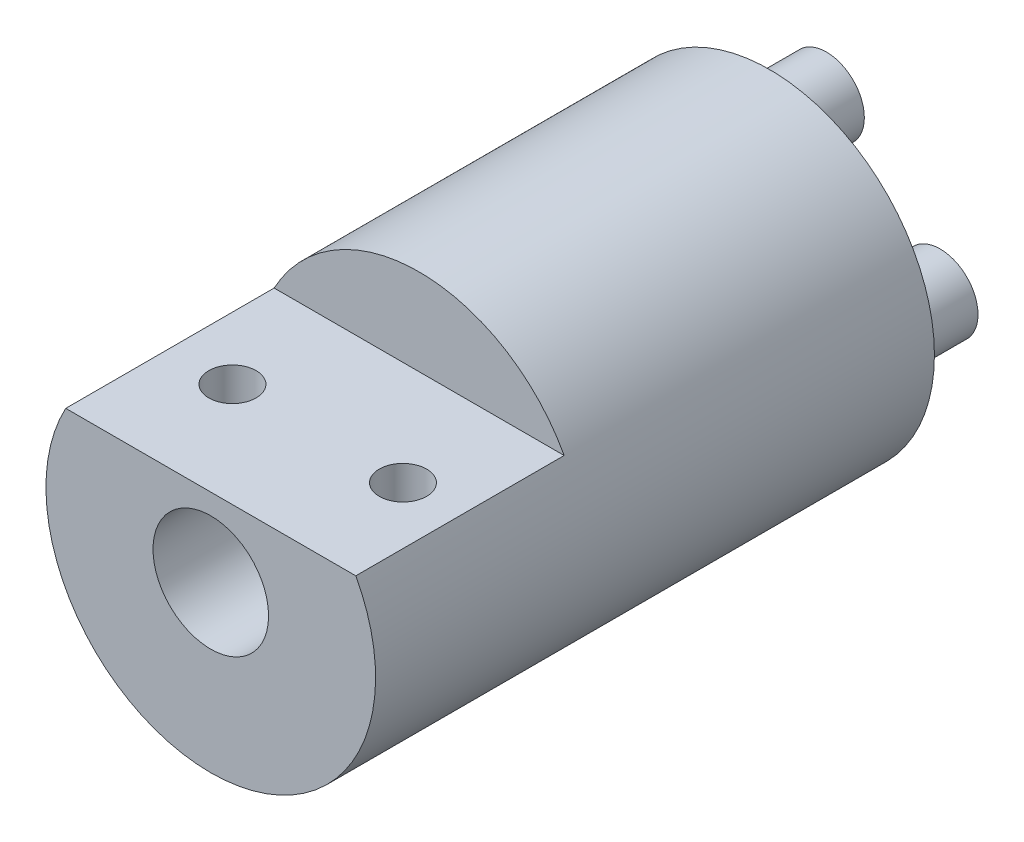
SolidWorks part; units mm, degrees
ref_plane "Front Plane" through (0, 0, 0) normal (0, 0, 1) x (1, 0, 0)
ref_plane "Top Plane" through (0, 0, 0) normal (0, 1, 0) x (1, 0, 0)
ref_plane "Right Plane" through (0, 0, 0) normal (1, 0, 0) x (0, 0, -1)
sketch "Sketch1" plane through (0, 0, 0) normal (0, 0, 1) x (1, 0, 0)
  circle A0 centre (0, 0) radius 8.7
  dimension "D1" = 17.4
extrude "Boss-Extrude1" add sketch "Sketch1" along normal blind 29.5 contours A0
sketch "Sketch2" plane through (0, 0, 29.5) normal (0, 0, 1) x (1, 0, 0)
  line L1 (-7.6555, 8.7) -> (9.3445, 8.7)
  line L2 (-7.6555, 8.7) -> (-7.6555, 4.1331)
  line L3 (-7.6555, 4.1331) -> (9.3445, 4.1331)
  line L4 (9.3445, 8.7) -> (9.3445, 4.1331)
  circle A0 centre (0, 0) radius 8.7 construction
  dimension "D1" = 17
sketch "Sketch4" plane through (0, 0, 0) normal (0, 0, -1) x (-1, 0, 0)
  circle A0 centre (0, 6) radius 2
  circle A1 centre (6, 0) radius 2
  circle A2 centre (0, -6) radius 2
  circle A3 centre (-6, 0) radius 2
  dimension "D1" = 4
  dimension "D2" = 6
  dimension "D3" = 6
  dimension "D4" = 6
  dimension "D5" = 6
sketch "Sketch5" plane through (0, 0, 0) normal (0, 0, -1) x (-1, 0, 0)
  circle A0 centre (0, 0) radius 1.75
  dimension "D1" = 3.5
extrude "Cut-Extrude1" cut sketch "Sketch5" against normal through all
sketch "Sketch6" plane through (0, 0, 29.5) normal (0, 0, 1) x (1, 0, 0)
  circle A0 centre (0, 0) radius 3.05
  dimension "D1" = 6.1
extrude "Cut-Extrude3" cut sketch "Sketch6" against normal offset from surface (26.5 mm away) 3 up to face at (-1.75, 0, 0)
extrude "Cut-Extrude4" cut sketch "Sketch2" against normal blind 11 contours L1 L4 L3 L2
fillet "Fillet1" radius 0.3 1 edges at (1.75, 0, 3)
hole_wizard "Tap Drill for M3x0.5 Tap1" positions "Sketch7" profile "Sketch8" hole size "M3x0.5" standard "ANSI Metric" end condition through all
sketch "Sketch7" plane through (0, 4.1331, 0) normal (0, 1, 0) x (1, 0, 0)
  line L0 (-7.6555, -29.5) -> (7.6555, -29.5) construction
  line L1 (-7.6555, -18.5) -> (-7.6555, -29.5) construction
  point P0 (4.6445, -24)
  point P2 (-4.3555, -24)
  dimension "D1" = 9
  dimension "D2" = 5.5
  dimension "D3" = 3.3
sketch "Sketch8" plane through (4.6445, 4.1331, 24) normal (1, 0, 0) x (0, 0, 1)
  line L0 (0, 0) -> (0, 12.8331)
  line L1 (0, 12.8331) -> (1.25, 12.8331)
  line L2 (1.25, 12.8331) -> (1.25, 0)
  line L5 (1.25, 0) -> (0, 0)
  line L11 (0, -6.35) -> (0, 107.95) construction
  dimension "Thru Hole Dia." = 2.5
  dimension "Thru Hole Depth" = 12.8331
extrude "Boss-Extrude2" add sketch "Sketch4" along normal blind 3
